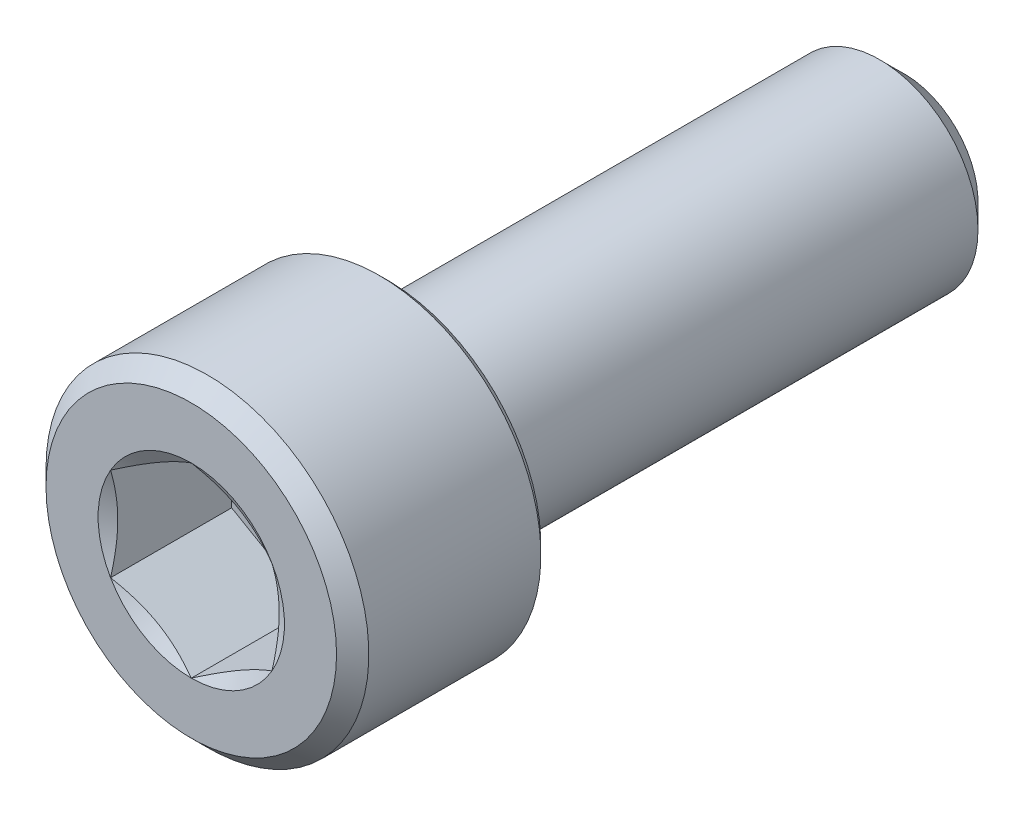
SolidWorks part; units mm, degrees
ref_plane "Front Plane" through (0, 0, 0) normal (0, 0, 1) x (1, 0, 0)
ref_plane "Top Plane" through (0, 0, 0) normal (0, 1, 0) x (1, 0, 0)
ref_plane "Right Plane" through (0, 0, 0) normal (1, 0, 0) x (0, 0, -1)
sketch "Sketch1" plane through (0, 0, 0) normal (1, 0, 0) x (0, 0, -1)
  line L0 (8.763, 0) -> (-8.763, 0) construction
  line L1 (-8.763, 0) -> (-8.763, 3.9687) construction
  line L2 (-3.937, 2.413) -> (-3.937, 0) construction
  line L3 (7.9693, 0) -> (7.9693, 0.7937) construction
  line L4 (-3.937, 0) -> (-3.937, -2.413) construction
  point P6 (-8.763, 1.9844)
  point P9 (-8.763, -1.9844)
  point P10 (-3.937, 0)
  point P13 (5.9849, -2.413)
  dimension "D1" = 0.7937
  dimension "D2" = 2.7781
sketch "Sketch2" plane through (0, 0, 0) normal (1, 0, 0) x (0, 0, -1)
  line L0 (8.763, 1.8177) -> (8.1677, 2.413)
  line L1 (-8.763, 3.9687) -> (-3.937, 3.9687)
  line L2 (-8.763, 3.9687) -> (-8.763, 0)
  line L4 (-3.937, 3.9687) -> (-3.937, 2.413)
  line L5 (-3.937, 2.413) -> (8.1677, 2.413)
  line L8 (8.763, 1.8177) -> (8.763, 0)
  line L9 (8.763, 0) -> (-8.763, 0) construction
  line L10 (8.763, 0) -> (-8.763, 0)
  dimension "D1" = 135
  dimension "D2" = 0.5953
revolve "Revolve1" add sketch "Sketch2" angle 360 about L10
sketch "Sketch4" plane through (0, 0, 8.763) normal (0, 0, 1) x (1, 0, 0)
  line L1 (0, 2.2914) -> (-1.9844, 1.1457)
  line L2 (-1.9844, 1.1457) -> (-1.9844, -1.1457)
  line L3 (-1.9844, -1.1457) -> (0, -2.2914)
  line L4 (0, -2.2914) -> (1.9844, -1.1457)
  line L5 (1.9844, -1.1457) -> (1.9844, 1.1457)
  line L6 (1.9844, 1.1457) -> (0, 2.2914)
  circle A0 centre (0, 0) radius 1.9844 construction
  circle A1 centre (0, 0) radius 3.9687 construction
  circle A2 centre (0, 0) radius 3.9687 construction
  dimension "D1" = 3.9688
extrude "Cut-Extrude1" cut sketch "Sketch4" against normal blind 2.9766
sketch "Sketch5" plane through (0, 0, 8.763) normal (0, 0, 1) x (1, 0, 0)
  circle A0 centre (0, 0) radius 2.2914
extrude "Cut-Extrude2" cut sketch "Sketch5" against normal blind 10 draft 60
chamfer "Chamfer1" distance 0.3969 angle 45 1 edges at (-3.9687, 0, 8.763)
chamfer "Chamfer2" distance 0.1984 angle 45 1 edges at (-3.9687, 0, 3.937)
sketch "Sketch3" [suppressed] plane through (0, 0, -8.763) normal (0, 0, -1) x (-1, 0, 0)
  circle A0 centre (0, 0) radius 2.413 construction
  circle A1 centre (0, 0) radius 2.413
ref_axis "Center Axis1" through (0, 0, -5.7312) along (0, 0, 1)
ref_plane "Contact Plane1" through (0, 0, -8.763) normal (0, 0, 1) x (1, 0, 0)
ref_plane "Contact Plane2" through (0, 0, 3.937) normal (0, 0, 1) x (1, 0, 0)
split "Split1" [suppressed] bodies to split 106
curve "Helix/Spiral1" [suppressed] pitch 0.7937 height 13.4937 turns 17
sketch "Sketch7" [suppressed] plane through (0, 0, 0) normal (1, 0, 0) x (0, 0, -1)
  line L0 (8.7134, 2.4989) -> (9.1103, 1.8115) construction
  line L1 (9.1103, 1.8115) -> (9.5071, 2.4989) construction
  line L2 (9.5071, 2.4989) -> (8.7134, 2.4989) construction
  line L3 (8.763, 2.413) -> (9.4575, 2.413)
  line L4 (9.1103, 2.4989) -> (9.1103, 2.413) construction
  line L5 (9.1103, 2.413) -> (9.1103, 1.8974) construction
  line L6 (9.1103, 1.8974) -> (9.1103, 1.8115) construction
  line L7 (9.0607, 1.8974) -> (9.1599, 1.8974)
  line L8 (8.7382, 2.456) -> (9.4823, 2.456) construction
  line L9 (9.1599, 1.8974) -> (9.4575, 2.413)
  line L10 (9.0607, 1.8974) -> (8.763, 2.413)
  point P0 (9.1103, 2.456)
  dimension "D1" = 0.7937
  dimension "D2" = 0.0992
sweep "Cut-Sweep1" [suppressed] cut profiles "Sketch7" path "Helix/Spiral1"
sketch "Sketch11" [suppressed] plane through (0, 0, 3.937) normal (0, 0, -1) x (-1, 0, 0)
  circle A0 centre (0, 0) radius 2.413
extrude "Boss-Extrude4" [suppressed] add sketch "Sketch11" along normal through all draft 45
sketch "Sketch9" [suppressed] plane through (0, 0, 3.937) normal (0, 0, -1) x (-1, 0, 0)
  line L0 (0, 0) -> (0, 3.9687) construction
  line L1 (0, 3.7703) -> (-0.416, 4.1672)
  line L2 (-0.416, 4.1672) -> (0.416, 4.1672)
  line L3 (0.416, 4.1672) -> (0, 3.7703)
  line L4 (-0.208, 3.9688) -> (0, 0) construction
  line L5 (0, 0) -> (0.208, 3.9688) construction
  circle A0 centre (0, 0) radius 3.9687 construction
  circle A1 centre (0, 0) radius 3.7703 construction
  dimension "D1" = 0.3969
  dimension "D2" = 6
extrude "Cut-Extrude3" [suppressed] cut sketch "Sketch9" against normal up to next
pattern_circular "CirPattern1" [suppressed] count 60 over 360 of bodies 112
equation "\"D1@Sketch1\"=\"Pitch@Sketch1\""
equation "\"D2@Sketch2\"=\"D1@Sketch1\"*.75"
equation "\"D4@Helix/Spiral1\"=\"Pitch@Sketch1\""
equation "\"D3@Helix/Spiral1\"=\"Length@Sketch1\"+\"Pitch@Sketch1\""
equation "\"D1@Sketch4\" = \"Drive Size@Sketch1\""
equation "\"D1@Cut-Extrude1\"=\"D1@Sketch4\"*.75"
equation "\"D19\"= \"D1@Sketch4\" * .75"
equation "\"D1@Chamfer1\" = \"Head Diameter@Sketch1\" * .05"
equation "\"D1@Chamfer2\"=\"D1@Chamfer1\"/2"
equation "\"D2@Sketch7\"=\"D1@Sketch7\"/8"
equation "\"D1@Sketch7\"=\"D4@Helix/Spiral1\""
equation "\"D2@Sketch1\"=\"Pitch@Sketch1\"*3.5"
equation "\"D1@Sketch9\"=\"D1@Chamfer1\""
equation "\"D1@CirPattern1\"=\"D3@CirPattern1\"/\"D2@Sketch9\""
